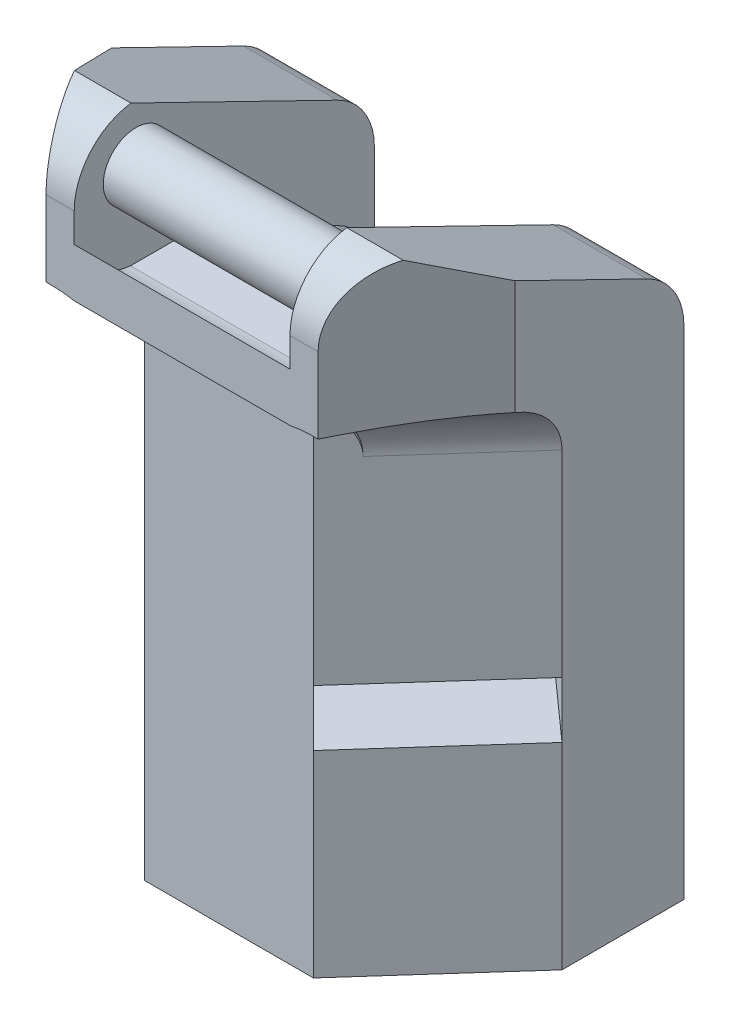
SolidWorks part; units mm, degrees
ref_plane "Front Plane" through (0, 0, 0) normal (0, 0, 1) x (1, 0, 0)
ref_plane "Top Plane" through (0, 0, 0) normal (0, 1, 0) x (1, 0, 0)
ref_plane "Right Plane" through (0, 0, 0) normal (1, 0, 0) x (0, 0, -1)
sketch "Sketch1" plane through (0, 0, 0) normal (0, 1, 0) x (1, 0, 0)
  line L0 (-30.5, 27) -> (12.5, 27)
  line L1 (12.5, 27) -> (12.5, 14)
  line L2 (12.5, 14) -> (0, 0)
  line L3 (0, 0) -> (-18, 0)
  line L4 (-18, 0) -> (-30.5, 14)
  line L5 (-30.5, 14) -> (-30.5, 27)
  dimension "D1" = 43
  dimension "D2" = 13
  dimension "D3" = 14
  dimension "D4" = 18
  dimension "D5" = 12.5
  dimension "D6" = 13
extrude "Boss-Extrude1" add sketch "Sketch1" along normal blind 30
sketch "Sketch6" plane through (0, 0, 0) normal (0, -1, 0) x (1, 0, 0)
  line L0 (12.5, -27) -> (-30.5, -27) construction
  line L2 (12.5, -14) -> (12.5, -27) construction
  circle A0 centre (-9, -18) radius 7.75
  dimension "D2" = 15.5
  dimension "D1" = 9
  dimension "D3" = 21.5
extrude "Cut-Extrude3" cut sketch "Sketch6" against normal blind 0.5
sketch "Sketch7" plane through (0, 30, 0) normal (0, 1, 0) x (1, 0, 0)
  line L6 (-30.5, 27) -> (-30.5, 14)
  line L7 (-30.5, 14) -> (-18, 0)
  line L8 (-18, 0) -> (0, 0)
  line L9 (0, 0) -> (12.5, 14)
  line L10 (12.5, 14) -> (12.5, 27)
  line L11 (12.5, 27) -> (-30.5, 27)
  line L12 (-30.5, 27) -> (-30.5, 14)
  line L13 (-30.5, 14) -> (-18, 0)
  line L14 (-18, 0) -> (0, 0)
  line L15 (0, 0) -> (12.5, 14)
  line L16 (12.5, 14) -> (12.5, 27)
  line L17 (12.5, 27) -> (-30.5, 27)
  dimension "D1" = 0
extrude "Boss-Extrude2" add sketch "Sketch7" along normal blind 15
sketch "Sketch8" plane through (0, 45, 0) normal (0, 1, 0) x (1, 0, 0)
  line L0 (-20.5, 0) -> (2.5, 0) construction
  line L1 (-16.5, 0) -> (16.5, 0) construction
  line L2 (-9, 27) -> (-9, 0) construction
  line L3 (12.5, 27) -> (-30.5, 27) construction
  line L6 (-30.5, 27) -> (-30.5, 9)
  line L8 (-30.5, 27) -> (-20.5, 27)
  line L10 (-30.5, 27) -> (-30.5, 14) construction
  line L11 (-20.5, 27) -> (-20.5, -5)
  line L12 (-20.5, -5) -> (-23.5, -5)
  line L13 (-23.5, -5) -> (-30.5, 9)
  point P18 (-9, 27)
  dimension "D1" = 23
  dimension "D2" = 18
  dimension "D3" = 32
  dimension "D4" = 3
extrude "Boss-Extrude3" add sketch "Sketch8" along normal blind 15
ref_plane "Plane1" through (-9, 0, 0) normal (1, 0, 0) x (0, 0, -1)
chamfer "Chamfer1" distance 5 angle 64 1 edges at (-4, 45, -27) first distance on face at (-12.8333, 35, -27)
sketch "Sketch10" plane through (-20.5, 0, 0) normal (1, 0, 0) x (0, 0, -1)
  line L0 (-5, 60) -> (-5, 53.9685) construction
  line L1 (-5, 60) -> (-5, 45) construction
  line L2 (-5, 53.9685) -> (1.5947, 53.9685) construction
  circle A0 centre (1.5947, 53.9685) radius 3.5
sketch "Sketch12" plane through (0, 45, 0) normal (0, 1, 0) x (1, 0, 0)
  line L0 (-9, 26.6347) -> (-9, -7.2493) construction
  line L2 (-30.5, 9) -> (-23.5, -5) construction
  line L5 (-20.5, -5) -> (-20.5, 2.8) construction
  line L6 (12.5, 9) -> (12.5, 27)
  line L7 (2.5, -5) -> (2.5, 27)
  line L8 (-20.5, 27) -> (12.5, 27) construction
  line L9 (2.5, 27) -> (12.5, 27)
  line L12 (12.5, 9) -> (5.5, -5)
  line L13 (5.5, -5) -> (2.5, -5)
extrude "Boss-Extrude5" add sketch "Sketch12" along direction (0, -1, 0) on the side of the normal up to surface (15 mm away) up to face at (-25.1, 60, -10.6)
extrude "Boss-Extrude6" add sketch "Sketch10" along normal up to next
sketch "Sketch18" plane through (0, 45, 0) normal (0, -1, 0) x (1, 0, 0)
  line L4 (12.5, -16.7485) -> (2.5, -16.7485)
  line L5 (2.5, -16.7485) -> (2.5, -27)
  line L6 (2.5, -27) -> (12.5, -27)
  line L7 (12.5, -27) -> (12.5, -16.7485)
  line L8 (12.5, -16.7485) -> (2.5, -16.7485)
  line L9 (2.5, -16.7485) -> (2.5, -27)
  line L10 (2.5, -27) -> (12.5, -27)
  line L11 (12.5, -27) -> (12.5, -16.7485)
  dimension "D1" = 0
extrude "Boss-Extrude7" add sketch "Sketch18" along normal up to surface (5 mm away) up to face at (-2.7, 43, -20.8491)
sketch "Sketch19" plane through (-20.5, 0, 0) normal (1, 0, 0) x (0, 0, -1)
  line L0 (1.0524, 60) -> (27, 47.3445)
  line L1 (-5, 60) -> (27, 60) construction
  line L2 (27, 60) -> (27, 40) construction
  line L3 (16.7485, 45) -> (27, 40) construction
  line L4 (16.7485, 45) -> (27, 40) construction
  line L5 (1.0524, 60) -> (1.0524, 61.7519)
  line L6 (1.0524, 61.7519) -> (30.6793, 60.876)
  line L7 (30.6793, 60.876) -> (27, 47.3445)
extrude "Cut-Extrude4" cut sketch "Sketch19" against normal through all both and the other way through all
fillet "Fillet4" radius 7 1 edges at (-22, 60, 5)
fillet "Fillet5" radius 7 1 edges at (4, 60, 5)
fillet "Fillet6" radius 7 1 edges at (7.5, 45, -8.4)
fillet "Fillet7" radius 7 1 edges at (-25.5, 45, -8.4)
sketch "Sketch21" plane through (-20.5, 0, 0) normal (1, 0, 0) x (0, 0, -1)
  line L0 (2.8, 45) -> (-5, 45)
  line L1 (-5, 53.0644) -> (-5, 44.7633) construction
  line L2 (-5, 45) -> (-5, 44.7633)
  line L7 (-5, 53.0644) -> (-5, 44.7633)
  line L8 (2.8, 38) -> (2.8, 45)
  line L9 (2.8, 45) -> (16.7485, 45)
  line L10 (16.7485, 45) -> (27, 40)
  line L11 (27, 40) -> (27, 47.3445)
  line L14 (2.8, 38) -> (2.8, 45)
  line L18 (27, 47.3445) -> (1.0524, 60)
  arc A1 (1.0524, 60) -> (-5, 53.0644) centre (2, 53.0644) ccw
  ellipse E1 centre (-7.7103, 38) end of major axis (2.8, 38) minor radius 7 (2.8, 38) -> (-5, 44.7633) ccw
  ellipse E2 centre (-7.7103, 38) end of major axis (2.8, 38) minor radius 7 (2.8, 38) -> (-5, 44.7633) ccw
  dimension "D1" = 0
extrude "Boss-Extrude8" add sketch "Sketch21" along normal up to next contours L0 L2 E2 L14
fillet "Fillet9" radius 7 3 edges at (-25.5, 47.3445, -27) (7.5, 47.3445, -27) (-9, 40, -27)
sketch "Sketch22" plane through (2.5, 0, 0) normal (-1, 0, 0) x (0, 0, 1)
  line L0 (-1.0524, 60) -> (-23.0686, 49.262) construction
  line L1 (-1.0524, 60) -> (-23.0686, 49.262) construction
  line L2 (5, 51.3745) -> (-27, 35.7671)
  line L3 (5, 53.0644) -> (5, 45) construction
  line L4 (-27, 42.9704) -> (-27, 0) construction
  line L5 (-27, 35.7671) -> (-27, 42.9704)
  line L6 (-27, 42.9704) -> (-2.0184, 49.6668)
  line L7 (-2.0184, 49.6668) -> (5, 51.3745)
extrude "Cut-Extrude5" cut sketch "Sketch22" along normal up to surface (23 mm away) up to face at (-20.5, 53.9685, 1.9053)
fillet "Fillet12" radius 7 2 edges at (-9, 35.7678, -26.9986) (-9, 45, -8.0697)
sketch "Sketch23" plane through (2.5, 0, 0) normal (-1, 0, 0) x (0, 0, 1)
  line L0 (5, 45) -> (-1, 45)
  line L1 (5, 53.0644) -> (5, 45) construction
  line L2 (5, 49.9698) -> (5, 45)
  arc A0 (-1, 45) -> (5, 49.9698) centre (-1.71, 51.9639) ccw
  dimension "D2" = 7
  dimension "D1" = 6
extrude "Boss-Extrude9" add sketch "Sketch23" along normal up to next
sketch "Sketch24" plane through (0, 0, 0) normal (0, -1, 0) x (1, 0, 0)
  line L6 (-30.5, -14) -> (-30.5, -27)
  line L7 (-30.5, -27) -> (12.5, -27)
  line L8 (12.5, -27) -> (12.5, -14)
  line L9 (12.5, -14) -> (0, 0)
  line L10 (0, 0) -> (-18, 0)
  line L11 (-18, 0) -> (-30.5, -14)
  line L12 (-30.5, -14) -> (-30.5, -27)
  line L13 (-30.5, -27) -> (12.5, -27)
  line L14 (12.5, -27) -> (12.5, -14)
  line L15 (12.5, -14) -> (0, 0)
  line L16 (0, 0) -> (-18, 0)
  line L17 (-18, 0) -> (-30.5, -14)
  circle A0 centre (-9, -18) radius 7.75 construction
  circle A1 centre (-9, -18) radius 7.75
  dimension "D1" = 0
extrude "Boss-Extrude10" add sketch "Sketch24" along normal blind 10
sketch "Sketch25" plane through (0, 0, 0) normal (0.7459, 0, 0.666) x (0.666, 0, -0.7459)
  line L0 (-0.1732, -10) -> (0, 10.9993) construction
  line L1 (0, 42.7571) -> (0, -10) construction
  line L2 (18.7683, 38) -> (18.7683, -10) construction
  line L3 (0, 10.9993) -> (18.7683, 10.9993)
  line L4 (0, 10.9993) -> (0, 16.9993)
  line L5 (0, 16.9993) -> (18.7683, 16.9993)
  line L6 (18.7683, 10.9993) -> (18.7683, 16.9993)
  dimension "D1" = 6
  dimension "D2" = 20.9993
extrude "Cut-Extrude6" cut sketch "Sketch25" against normal blind 10
sketch "Sketch26" plane through (-10.0156, 0, 8.9425) normal (-0.7459, 0, 0.666) x (0.666, 0, 0.7459)
  line L0 (-30.7566, -10) -> (-30.7566, 11) construction
  line L1 (-30.7566, 38) -> (-30.7566, -10) construction
  line L2 (-11.9883, 42.7571) -> (-11.9883, -10) construction
  line L3 (-30.7566, 11) -> (-11.9883, 11)
  line L4 (-30.7566, 11) -> (-30.7566, 17)
  line L5 (-30.7566, 17) -> (-11.9883, 17)
  line L6 (-11.9883, 11) -> (-11.9883, 17)
  dimension "D1" = 21
  dimension "D2" = 6
extrude "Cut-Extrude7" cut sketch "Sketch26" against normal blind 10
